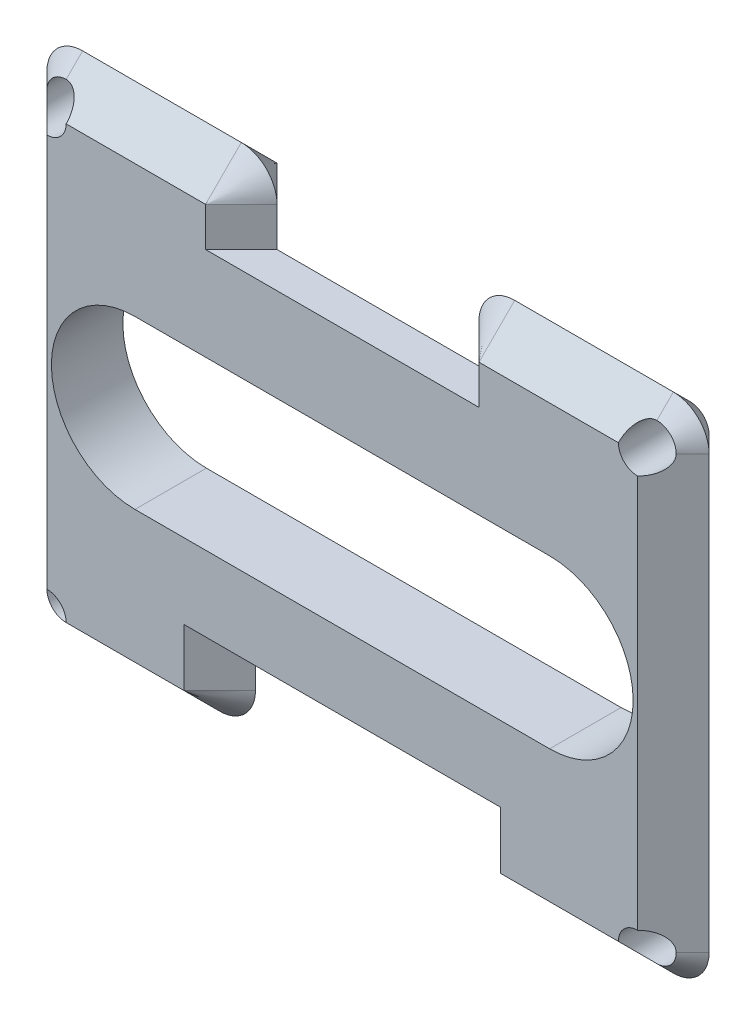
SolidWorks part; units mm, degrees
ref_plane "Front Plane" through (0, 0, 0) normal (0, 0, 1) x (1, 0, 0)
ref_plane "Top Plane" through (0, 0, 0) normal (0, 1, 0) x (1, 0, 0)
ref_plane "Right Plane" through (0, 0, 0) normal (1, 0, 0) x (0, 0, -1)
sketch "Sketch2" plane through (0, 0, 0) normal (0, 0, 1) x (1, 0, 0)
  line L0 (-58.0246, 0) -> (58.0246, 0) construction
  line L1 (-82.6662, 70.4379) -> (-38.2599, 70.4379)
  line L2 (-92.6662, 60.4379) -> (-92.6662, -60.4379)
  line L3 (-82.6662, -70.4379) -> (-44.2972, -70.4379)
  line L4 (92.6662, 60.4379) -> (92.6662, -60.4379)
  line L5 (-92.6662, 70.4379) -> (92.6662, -70.4379) construction
  line L6 (-92.6662, -70.4379) -> (92.6662, 70.4379) construction
  line L7 (-58.0246, 23.3831) -> (58.0246, 23.3831)
  line L8 (-58.0246, -23.3831) -> (58.0246, -23.3831)
  line L9 (38.2599, 70.4379) -> (82.6662, 70.4379)
  line L10 (-28.2599, 49.4928) -> (28.2599, 49.4928)
  line L11 (-28.2599, 49.4928) -> (-28.2599, 60.4379)
  line L13 (28.2599, 49.4928) -> (28.2599, 60.4379)
  line L14 (44.2972, -70.4379) -> (82.6662, -70.4379)
  line L16 (-34.2972, -60.4379) -> (-34.2972, -54.4097)
  line L17 (-34.2972, -54.4097) -> (34.2972, -54.4097)
  line L18 (34.2972, -60.4379) -> (34.2972, -54.4097)
  arc A0 (-58.0246, 23.3831) -> (-58.0246, -23.3831) centre (-58.0246, 0) ccw
  arc A1 (58.0246, -23.3831) -> (58.0246, 23.3831) centre (58.0246, 0) ccw
  arc A2 (82.6662, -70.4379) -> (92.6662, -60.4379) centre (82.6662, -60.4379) ccw
  arc A3 (-92.6662, -60.4379) -> (-82.6662, -70.4379) centre (-82.6662, -60.4379) ccw
  arc A4 (82.6662, 70.4379) -> (92.6662, 60.4379) centre (82.6662, 60.4379) cw
  arc A5 (-82.6662, 70.4379) -> (-92.6662, 60.4379) centre (-82.6662, 60.4379) ccw
  circle A6 centre (82.6662, -60.4379) radius 5.3939
  circle A7 centre (82.6662, 60.4379) radius 5.3939
  circle A8 centre (-82.6662, 60.4379) radius 5.3939
  circle A9 centre (-82.6662, -60.4379) radius 5.3939
  arc A10 (44.2972, -70.4379) -> (34.2972, -60.4379) centre (44.2972, -60.4379) cw
  arc A11 (-44.2972, -70.4379) -> (-34.2972, -60.4379) centre (-44.2972, -60.4379) ccw
  arc A12 (28.2599, 60.4379) -> (38.2599, 70.4379) centre (38.2599, 60.4379) cw
  arc A13 (-28.2599, 60.4379) -> (-38.2599, 70.4379) centre (-38.2599, 60.4379) ccw
  point P0 (0, 0)
  point P8 (0, 0)
  point P29 (0, 70.4379)
  point P30 (0, -70.4379)
  point P45 (28.2599, 70.4379)
  dimension "D1" = 10
  dimension "D2" = 10
  dimension "D3" = 10
extrude "Boss-Extrude1" add sketch "Sketch2" along normal blind 10
extrude "Boss-Extrude2" add sketch "Sketch2<2>" along normal blind 20
sketch "Sketch2<2>" plane through (0, 0, 0) normal (0, 0, 1) x (1, 0, 0) same geometry as "Sketch2"
chamfer "Chamfer1" distance 10 angle 45 10 edges at (34.2972, -57.4238, 0) (37.2261, -67.5089, 0) (63.4817, -70.4379, 0) (89.7373, -67.5089, 0) (92.6662, 0, 0) (89.7373, 67.5089, 0) (60.463, 70.4379, 0) (31.1888, 67.5089, 0) (0, 49.4928, 0) (28.2599, 54.9653, 0)
chamfer "Chamfer3" distance 10 angle 45 9 edges at (-34.2972, -57.4238, 0) (-37.2261, -67.5089, 0) (-63.4817, -70.4379, 0) (-89.7373, -67.5089, 0) (-92.6662, 0, 0) (-89.7373, 67.5089, 0) (-60.463, 70.4379, 0) (-31.1888, 67.5089, 0) (-28.2599, 49.9653, 0)
chamfer "Chamfer4" distance 10 angle 45 9 edges at (28.2599, 54.9653, 20) (31.1888, 67.5089, 20) (60.463, 70.4379, 20) (89.7373, 67.5089, 20) (92.6662, 0, 20) (89.7373, -67.5089, 20) (63.4817, -70.4379, 20) (37.2261, -67.5089, 20) (34.2972, -57.4238, 20)
chamfer "Chamfer5" distance 10 angle 45 1 edges at (5, -54.4097, 20)
chamfer "Chamfer6" distance 10 angle 45 9 edges at (-28.2599, 54.9653, 20) (-31.1888, 67.5089, 20) (-60.463, 70.4379, 20) (-89.7373, 67.5089, 20) (-92.6662, 0, 20) (-89.7373, -67.5089, 20) (-63.4817, -70.4379, 20) (-37.2261, -67.5089, 20) (-34.2972, -52.4238, 20)
